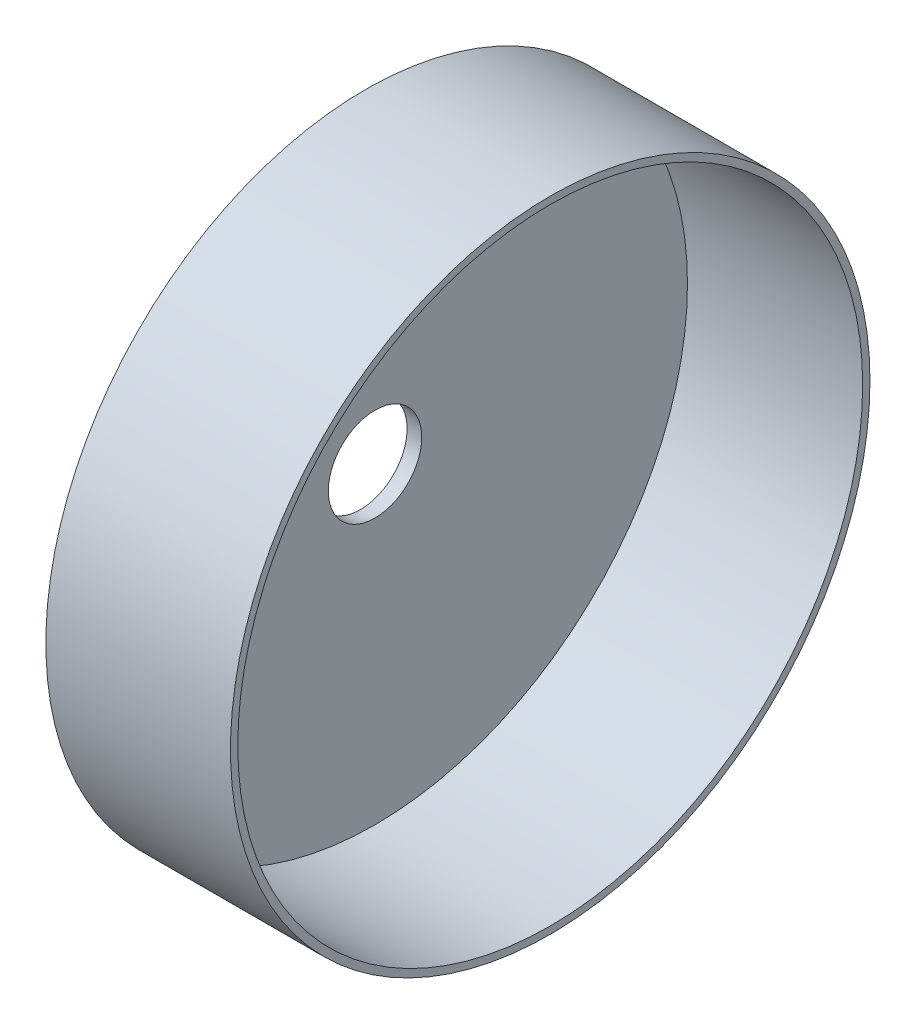
SolidWorks part; units mm, degrees
ref_plane "Front Plane" through (0, 0, 0) normal (1, 0, 0) x (0, 1, 0)
ref_plane "Top Plane" through (0, 0, 0) normal (0, 0, 1) x (0, 1, 0)
ref_plane "Right Plane" through (0, 0, 0) normal (0, 1, 0) x (-1, 0, 0)
sketch "Sketch1" plane through (0, 0, 0) normal (1, 0, 0) x (0, 1, 0)
  circle A0 centre (0, 0) radius 21.9
  dimension "D1" = 43.8
extrude "Boss-Extrude1" add sketch "Sketch1" along normal blind 1
sketch "Sketch2" plane through (1, 0, 0) normal (1, 0, 0) x (0, 1, 0)
  circle A0 centre (0, 0) radius 21.4
  circle A2 centre (0, 0) radius 21.9
  dimension "D1" = 42.8
extrude "Boss-Extrude2" add sketch "Sketch2" along normal blind 12
sketch "Sketch3" plane through (0, 0, 0) normal (-1, 0, 0) x (0, -1, 0)
  circle A0 centre (0, 0) radius 3.2
extrude "Cut-Extrude1" cut sketch "Sketch3" against normal blind 12
sketch "Sketch4" plane through (0, 0, 0) normal (-1, 0, 0) x (0, -1, 0)
  circle A0 centre (0, 0) radius 3.9
  circle A2 centre (0, 0) radius 3.2
  dimension "D1" = 7.8
chamfer "Chamfer1" distance 2 angle 10 1 edges at (0, 0, -21.9) first distance on face at (0, 0, 3.2)
